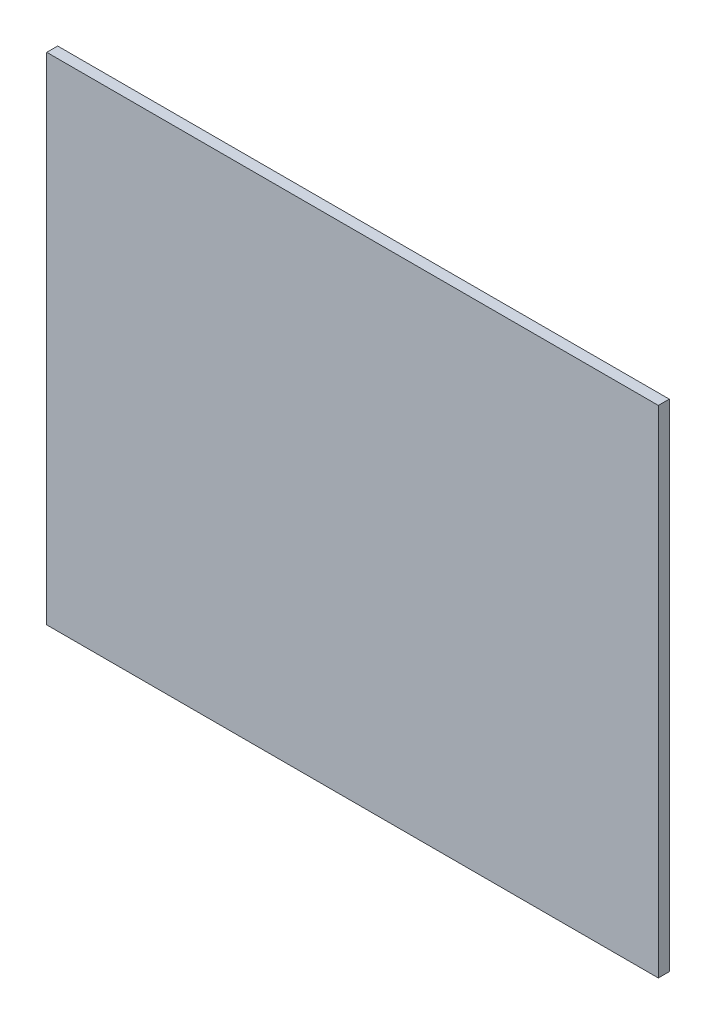
SolidWorks part; units mm, degrees
ref_plane "Front Plane" through (0, 0, 0) normal (0, 0, 1) x (1, 0, 0)
ref_plane "Top Plane" through (0, 0, 0) normal (0, 1, 0) x (1, 0, 0)
ref_plane "Right Plane" through (0, 0, 0) normal (1, 0, 0) x (0, 0, -1)
sketch "Sketch1" plane through (0, 0, 0) normal (0, 0, 1) x (1, 0, 0)
  line L1 (-73.1533, 40.2838) -> (111.8467, 40.2838)
  line L2 (-73.1533, 40.2838) -> (-73.1533, -109.7162)
  line L3 (-73.1533, -109.7162) -> (111.8467, -109.7162)
  line L4 (111.8467, 40.2838) -> (111.8467, -109.7162)
  dimension "D1" = 185
  dimension "D2" = 150
extrude "Boss-Extrude1" add sketch "Sketch1" along normal blind 3.302
